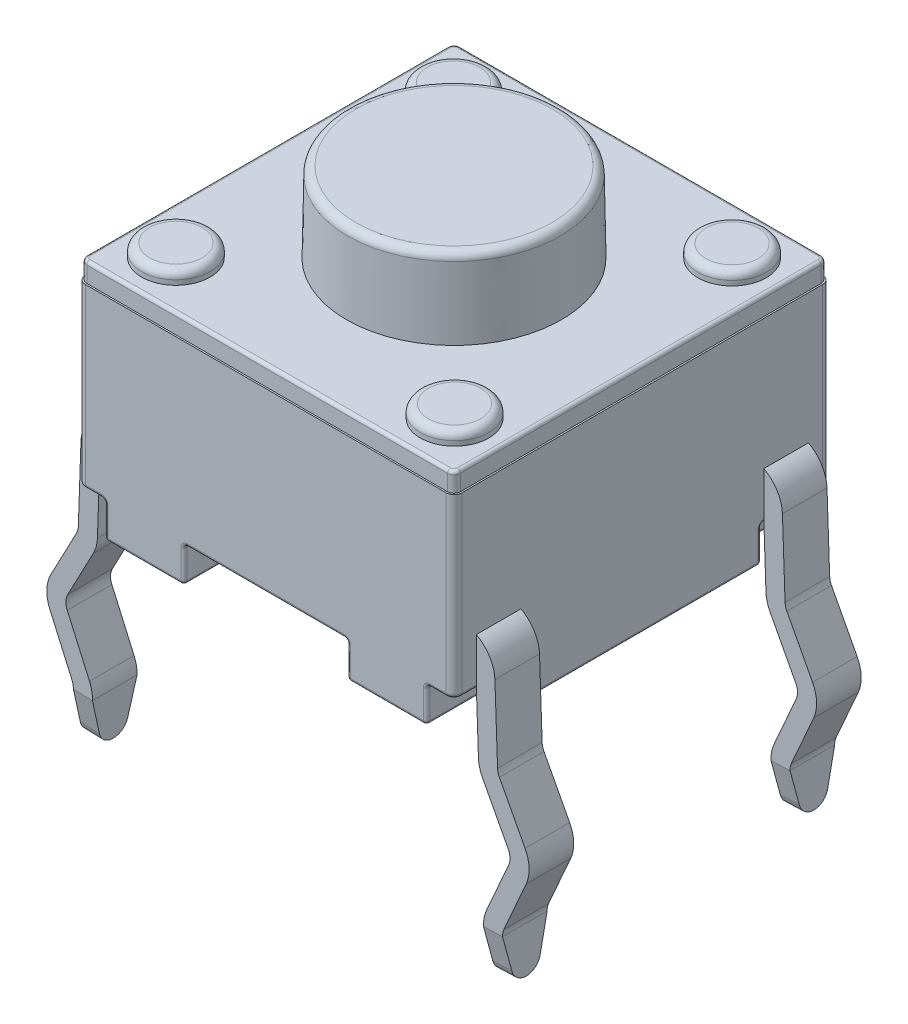
SolidWorks part; units mm, degrees
ref_plane "Front Plane" through (0, 0, 0) normal (0, 0, 1) x (1, 0, 0)
ref_plane "Top Plane" through (0, 0, 0) normal (0, 1, 0) x (1, 0, 0)
ref_plane "Right Plane" through (0, 0, 0) normal (1, 0, 0) x (0, 0, -1)
sketch "Sketch1" plane through (0, 0, 0) normal (0, 1, 0) x (1, 0, 0)
  line L1 (-3.0035, -3.0035) -> (3.0035, -3.0035)
  line L2 (-3.0035, -3.0035) -> (-3.0035, 3.0036)
  line L3 (-3.0035, 3.0036) -> (3.0035, 3.0036)
  line L4 (3.0035, -3.0035) -> (3.0035, 3.0036)
  line L5 (-3.0035, -3.0035) -> (3.0035, 3.0036) construction
  line L6 (-3.0035, 3.0036) -> (3.0035, -3.0035) construction
  point P0 (0, 0)
  dimension "D1" = 6.0071
  dimension "D2" = 6.0071
extrude "Boss-Extrude1" add sketch "Sketch1" along normal blind 2.8194 from offset 0.5588
fillet "Fillet1" radius 0.127 4 edges at (-3.0035, 1.9685, 3.0035) (-3.0035, 1.9685, -3.0036) (3.0035, 1.9685, -3.0036) (3.0035, 1.9685, 3.0035)
sketch "Sketch2" plane through (0, 3.3782, 0) normal (0, -1, 0) x (-1, 0, 0)
  line L8 (2.9781, -2.8765) -> (2.9781, 2.8765)
  line L9 (-2.8765, -2.9781) -> (2.8765, -2.9781)
  line L10 (-2.9781, 2.8765) -> (-2.9781, -2.8765)
  line L11 (2.8765, 2.9782) -> (-2.8765, 2.9782)
  line L12 (2.9781, -2.8765) -> (2.9781, 2.8765)
  line L13 (-2.8765, -2.9781) -> (2.8765, -2.9781)
  line L14 (-2.9781, 2.8765) -> (-2.9781, -2.8765)
  line L15 (2.8765, 2.9782) -> (-2.8765, 2.9782)
  arc A8 (2.8765, -2.9781) -> (2.9781, -2.8765) centre (2.8765, -2.8765) ccw
  arc A9 (-2.9781, -2.8765) -> (-2.8765, -2.9781) centre (-2.8765, -2.8765) ccw
  arc A10 (-2.8765, 2.9782) -> (-2.9781, 2.8765) centre (-2.8765, 2.8766) ccw
  arc A11 (2.9781, 2.8765) -> (2.8765, 2.9782) centre (2.8765, 2.8765) ccw
  arc A12 (2.8765, -2.9781) -> (2.9781, -2.8765) centre (2.8765, -2.8765) ccw
  arc A13 (-2.9781, -2.8765) -> (-2.8765, -2.9781) centre (-2.8765, -2.8765) ccw
  arc A14 (-2.8765, 2.9782) -> (-2.9781, 2.8765) centre (-2.8765, 2.8766) ccw
  arc A15 (2.9781, 2.8765) -> (2.8765, 2.9782) centre (2.8765, 2.8765) ccw
  dimension "D1" = 0.0254
extrude "Boss-Extrude2" add sketch "Sketch2" against normal blind 0.3048
sketch "Sketch3" plane through (0, 0, 0) normal (0, 1, 0) x (1, 0, 0)
  line L0 (-2.5662, -3.0035) -> (-2.5662, -1.8948)
  line L1 (-2.8765, -3.0035) -> (2.8765, -3.0035) construction
  line L2 (-2.5662, -1.8948) -> (-3.0035, -1.8948)
  line L3 (-3.0035, 2.8765) -> (-3.0035, -2.8765) construction
  line L4 (-2.4413, -0.5609) -> (-1.3018, -0.5609)
  line L5 (-1.3018, -0.5609) -> (-1.3017, -3.0035)
  line L6 (-2.4413, -0.5609) -> (-2.4413, 0.5609)
  line L7 (-2.5662, -3.0035) -> (-1.3017, -3.0035)
  line L8 (-3.0035, -1.8948) -> (-3.0035, 1.8948)
  line L9 (-2.4413, 0) -> (-3.0035, 0) construction
  line L10 (-2.5662, 3.0036) -> (-1.3017, 3.0035)
  line L11 (-1.3017, 0.5609) -> (-1.3017, 3.0035)
  line L12 (-2.4413, 0.5609) -> (-1.3017, 0.5609)
  line L13 (-2.5662, 1.8948) -> (-3.0035, 1.8948)
  line L14 (-2.5662, 3.0036) -> (-2.5662, 1.8948)
  line L15 (0, -3.0035) -> (0, 3.0036) construction
  line L16 (2.8765, 3.0036) -> (-2.8765, 3.0036) construction
  line L17 (2.4413, 0) -> (3.0035, 0) construction
  line L18 (2.5662, 3.0035) -> (2.5662, 1.8948)
  line L19 (2.5662, 1.8948) -> (3.0035, 1.8948)
  line L20 (2.4413, 0.5609) -> (1.3017, 0.5609)
  line L21 (1.3017, 0.5609) -> (1.3017, 3.0035)
  line L22 (2.5662, 3.0035) -> (1.3017, 3.0035)
  line L23 (3.0035, -1.8948) -> (3.0035, 1.8948)
  line L24 (2.5662, -3.0036) -> (1.3017, -3.0036)
  line L25 (2.4413, -0.5609) -> (2.4413, 0.5609)
  line L26 (1.3017, -0.5609) -> (1.3017, -3.0036)
  line L27 (2.4413, -0.5609) -> (1.3017, -0.5609)
  line L28 (2.5662, -1.8948) -> (3.0035, -1.8948)
  line L29 (2.5662, -3.0036) -> (2.5662, -1.8948)
  dimension "D1" = 1.7018
extrude "Boss-Extrude3" add sketch "Sketch3" along normal up to next
sketch "Sketch4" plane through (0, 3.683, 0) normal (0, 1, 0) x (1, 0, 0)
  line L1 (-2.2217, -2.2129) -> (2.2217, -2.2129) construction
  line L2 (-2.2217, -2.2129) -> (-2.2217, 2.2129) construction
  line L3 (-2.2217, 2.2129) -> (2.2217, 2.2129) construction
  line L4 (2.2217, -2.2129) -> (2.2217, 2.2129) construction
  line L5 (-2.2217, -2.2129) -> (2.2217, 2.2129) construction
  line L6 (-2.2217, 2.2129) -> (2.2217, -2.2129) construction
  circle A0 centre (2.2217, 2.2129) radius 0.5461
  circle A1 centre (-2.2217, 2.2129) radius 0.5461
  circle A2 centre (-2.2217, -2.2129) radius 0.5461
  circle A3 centre (2.2217, -2.2129) radius 0.5461
  point P0 (0, 0)
  dimension "D1" = 1.0922
extrude "Boss-Extrude4" add sketch "Sketch4" along normal blind 0.2032
sketch "Sketch5" plane through (0, 3.683, 0) normal (0, 1, 0) x (1, 0, 0)
  circle A0 centre (0, 0) radius 1.7145
  dimension "D1" = 3.429
extrude "Boss-Extrude5" add sketch "Sketch5" along normal blind 1.27 draft 1
fillet "Fillet2" radius 0.127 5 edges at (-2.2217, 3.8862, -1.6668) (-2.2217, 3.8862, 2.759) (2.2217, 3.8862, -1.6668) (2.2217, 3.8862, 2.759) (0, 4.953, 1.6923)
fillet "Fillet3" radius 0.0508 88 edges at (2.9664, 0.5588, 2.9664) (2.9664, 0.5588, -2.9664) (-2.9664, 0.5588, -2.9664) (-2.9664, 0.5588, 2.9664) (3.0035, 0.5588, 2.3857) (3.0035, 0.5588, -2.3857) (1.3017, 0.2794, 3.0036) (1.3017, 0.2794, -3.0035) (2.9484, 3.683, -2.9484) (0, 3.683, -2.9782) (-2.9484, 3.683, -2.9484) (-2.9781, 3.683, 0) (-2.9484, 3.683, 2.9484) (0, 3.683, 2.9781) (2.9484, 3.683, 2.9484) (2.4413, 0.2794, 0.5609) (1.3017, 0.2794, 0.5609) (1.3017, 0.2794, -0.5609) (2.4413, 0.2794, -0.5609) (-1.3018, 0.2794, 0.5609) (-2.4413, 0.2794, 0.5609) (-2.4413, 0.2794, -0.5609) (-1.3017, 0.2794, -0.5609) (2.7849, 0.5588, 1.8948) (3.0035, 0.2794, 1.8948) (2.5662, 0.2794, 3.0036) (2.5662, 0.5588, 2.4492) (2.5662, 0.2794, 1.8948) (3.0035, 0.2794, -1.8948) (2.7849, 0.5588, -1.8948) (2.5662, 0.2794, -1.8948) (2.5662, 0.5588, -2.4492) (2.5662, 0.2794, -3.0035) (-2.5662, 0.2794, -1.8948) (-2.5662, 0.2794, 1.8948) (-1.8715, 0.5588, -0.5609) (-2.4413, 0.5588, 0) (-1.8715, 0.5588, 0.5609) (1.3017, 0.5588, 1.7822) (1.8715, 0.5588, 0.5609) (2.4413, 0.5588, 0) (1.8715, 0.5588, -0.5609) (1.3017, 0.5588, -1.7822) (-1.3017, 0, 1.7822) (-1.8715, 0, 0.5609) (-2.4413, 0, 0) (-1.8715, 0, -0.5609) (-1.3017, 0, -1.7822) (-1.934, 0, -3.0035) (-2.5662, 0, -2.4492) (-2.7849, 0, -1.8948) (-3.0035, 0, 0) (-2.7849, 0, 1.8948) (-2.5662, 0, 2.4492) (-1.934, 0, 3.0035) (1.3017, 0, -1.7822) (1.8715, 0, -0.5609) (2.4413, 0, 0) (1.8715, 0, 0.5609) (1.3017, 0, 1.7822) (1.934, 0, 3.0036) (2.5662, 0, 2.4492) (2.7849, 0, 1.8948) (3.0035, 0, 0) (2.7849, 0, -1.8948) (2.5662, 0, -2.4492) (1.934, 0, -3.0035) (2.9781, 3.683, 0)
sketch "Sketch6" plane through (0, 0, 3.0035) normal (0, 0, 1) x (1, 0, 0)
  line L0 (-2.9873, 1.0641) -> (-3.0423, -0.5107)
  line L1 (-3.0423, -0.5107) -> (-3.5687, -1.5089)
  line L2 (-3.5687, -1.5089) -> (-3.1132, -2.5415)
  line L3 (-3.1132, -2.5415) -> (-3.1424, -3.3782)
  line L4 (-2.9873, 1.0641) -> (-2.5265, 1.0641)
  line L5 (-1.3525, 0) -> (-2.5154, 0) construction
  dimension "D1" = 4.445
  dimension "D2" = 3.3782
  dimension "D3" = 3.0226
  dimension "D4" = 3.5687
  dimension "D5" = 2.032
  dimension "D6" = 1.5748
  dimension "D7" = 92
extrude "Extrude-Thin1" add sketch "Sketch6" against normal blind 0.7112 from offset 0.3556 thin offset against normal yes
sketch "Sketch9" plane through (-3.3254, 0.1161, 0) normal (-0.9994, 0.0349, 0) x (0, 0, 1)
  line L0 (2.6479, -2.7766) -> (2.5175, -3.3091)
  line L1 (2.0672, -3.3091) -> (1.9367, -2.7766)
  line L2 (1.9367, -3.4858) -> (2.6479, -3.4858) construction
  line L3 (2.6479, -2.7766) -> (2.6479, -3.4858)
  line L4 (2.6479, -3.4858) -> (1.9367, -3.4858)
  line L5 (1.9367, -3.4858) -> (1.9367, -2.7766)
  arc A0 (2.5175, -3.3091) -> (2.0672, -3.3091) centre (2.2923, -3.254) cw
  line M1 (2.6479, -3.4858) -> (2.6479, -2.7766)
  line M3 (1.9367, -2.7766) -> (1.9367, -3.4858)
  line M4 (1.9367, -3.4858) -> (2.6479, -3.4858)
extrude "Cut-Extrude1" cut sketch "Sketch9" against normal blind 0.7112 contours L0 A0 L4 M1 | A0 L1 M4 M3
mirror "Mirror1" about plane through (0, 0, 0) normal (0, 0, 1) of "Cut-Extrude1", "Extrude-Thin1"
mirror "Mirror3" about plane through (0, 0, 0) normal (1, 0, 0) of "Mirror1", "Cut-Extrude1", "Extrude-Thin1"
